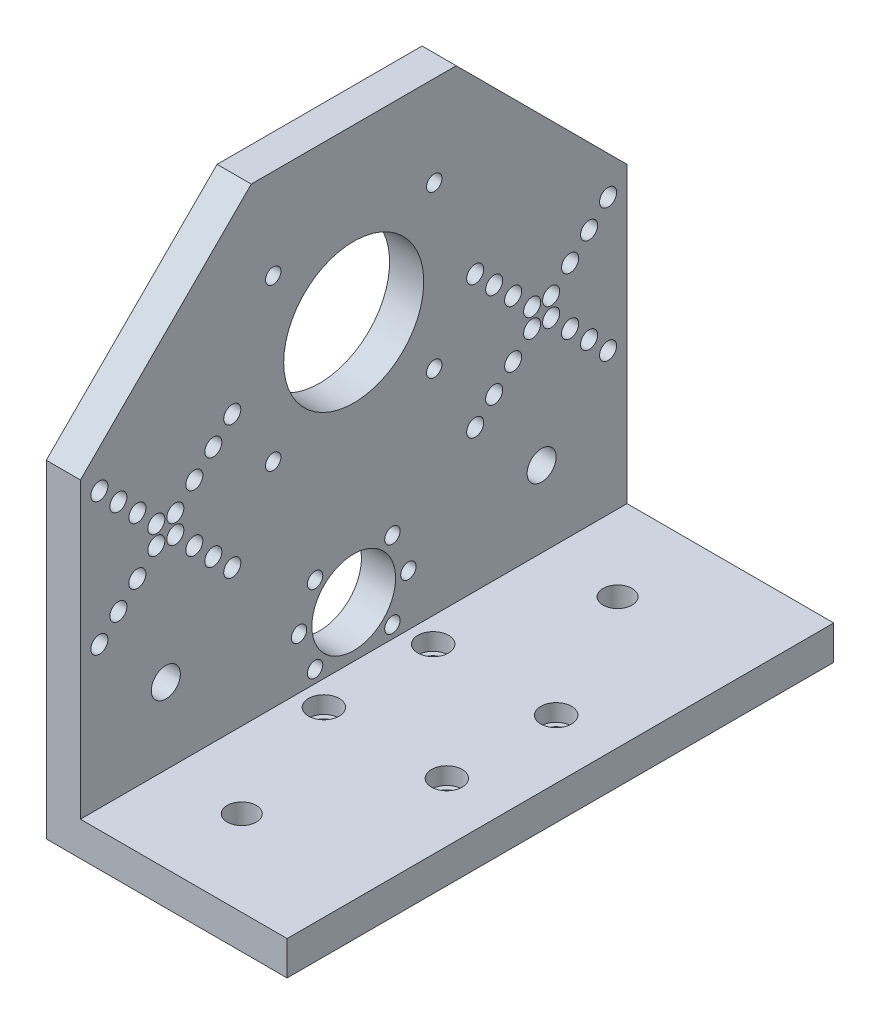
SolidWorks part; units mm, degrees
ref_plane "Front Plane" through (0, 0, 0) normal (0, 0, 1) x (1, 0, 0)
ref_plane "Top Plane" through (0, 0, 0) normal (0, 1, 0) x (1, 0, 0)
ref_plane "Right Plane" through (0, 0, 0) normal (1, 0, 0) x (0, 0, -1)
sketch "Sketch1" plane through (0, 0, 0) normal (0, 1, 0) x (1, 0, 0)
  line L0 (35.25, 46) -> (35.25, 14) construction
  line L1 (0, 0) -> (70.5, 0)
  line L2 (0, 0) -> (0, 60)
  line L3 (0, 60) -> (70.5, 60)
  line L4 (70.5, 0) -> (70.5, 60)
  line L5 (17.25, 46) -> (53.25, 46) construction
  line L6 (17.25, 46) -> (17.25, 14) construction
  line L7 (17.25, 14) -> (53.25, 14) construction
  line L8 (53.25, 46) -> (53.25, 14) construction
  line L9 (17.25, 30) -> (53.25, 30) construction
  circle A2 centre (53.25, 46) radius 2.95
  circle A4 centre (53.25, 14) radius 2.95
  circle A5 centre (17.25, 46) radius 2.95
  circle A6 centre (17.25, 14) radius 2.95
  dimension "D5" = 5.9
  dimension "D1" = 36
  dimension "D2" = 32
  dimension "D3" = 70.5
  dimension "D4" = 60
extrude "Boss-Extrude1" add sketch "Sketch1" along normal blind 10 contours L1 L4 L3 L2 A2 region at (35.25, 0, -30)
sketch "Sketch3" plane through (0, 10, 0) normal (0, 1, 0) x (1, 0, 0)
  circle A1 centre (53.25, 46) radius 4.5
  circle A5 centre (53.25, 14) radius 4.5
  circle A6 centre (17.25, 46) radius 4.5
  circle A7 centre (17.25, 14) radius 4.5
  dimension "D1" = 9
extrude "Cut-Extrude1" cut sketch "Sketch3" against normal blind 5
sketch "Sketch4" plane through (0, 10, 0) normal (0, 1, 0) x (1, 0, 0)
  line L0 (0, 30) -> (10, 30) construction
  line L1 (0, 60) -> (10, 60)
  line L2 (0, 60) -> (0, 0)
  line L3 (0, 0) -> (10, 0)
  line L4 (10, 60) -> (10, 0)
  line L5 (0, 60) -> (70.5, 60) construction
  line L6 (0, 0) -> (70.5, 0) construction
  circle A6 centre (53.25, 14) radius 4.5 construction
  dimension "D1" = 43.25
  dimension "D2" = 10
extrude "Boss-Extrude3" add sketch "Sketch4" along normal blind 31
sketch "Sketch5" plane through (0, 0, 0) normal (-1, 0, 0) x (0, 0, 1)
  line L0 (-30, 41) -> (-30, 10) construction
  line L1 (-60, 41) -> (0, 41) construction
  line L2 (-60, 10) -> (0, 10) construction
  line L3 (-60, 25) -> (0, 25) construction
  line L6 (-60, 41) -> (-60, 0) construction
  line L7 (-30, 25) -> (-18.6863, 36.3137) construction
  line L8 (0, 41) -> (0, 0) construction
  line L9 (0, 10) -> (-60, 10) construction
  line L10 (-30, 25) -> (-18.6863, 13.6863) construction
  circle A0 centre (-30, 25) radius 12.25
  circle A1 centre (-30, 25) radius 16 construction
  circle A2 centre (-14, 25) radius 2.25
  circle A3 centre (-18.6863, 36.3137) radius 2.25
  circle A4 centre (-18.6863, 13.6863) radius 2.25
  circle A5 centre (-41.3137, 36.3137) radius 2.25
  circle A6 centre (-46, 25) radius 2.25
  circle A7 centre (-41.3137, 13.6863) radius 2.25
  dimension "D1" = 24.5
  dimension "D2" = 32
  dimension "D3" = 4.5
  dimension "D5" = 15
  dimension "D6" = 45
  dimension "D7" = 45
  dimension "D4" = 2
extrude "Cut-Extrude2" cut sketch "Sketch5" against normal up to next
sketch "Sketch6" plane through (70.5, 0, 0) normal (1, 0, 0) x (0, 0, -1)
  line L1 (0, 41) -> (60, 41)
  line L2 (0, 41) -> (0, 10)
  line L3 (0, 10) -> (60, 10)
  line L4 (60, 41) -> (60, 10)
  circle A2 centre (30, 25) radius 8
  dimension "D1" = 16
extrude "Boss-Extrude4" add sketch "Sketch6" against normal blind 5
sketch "Sketch7" plane through (0, 41, 0) normal (0, 1, 0) x (1, 0, 0)
  line L1 (0, 60) -> (70.5, 60)
  line L2 (0, 60) -> (0, 0)
  line L3 (0, 0) -> (70.5, 0)
  line L4 (70.5, 60) -> (70.5, 0)
extrude "Boss-Extrude5" add sketch "Sketch7" along normal blind 5
sketch "Sketch8" plane through (0, 0, 0) normal (-1, 0, 0) x (0, 0, 1)
  line L1 (0, 46) -> (0, 0) construction
  line L2 (-60, 46) -> (0, 46)
  line L3 (-60, 46) -> (-60, 146)
  line L4 (-60, 146) -> (0, 146)
  line L5 (0, 46) -> (0, 146)
  line L6 (-53.57, 96) -> (-6.43, 96) construction
  line L7 (-53.57, 119.57) -> (-6.43, 119.57) construction
  line L8 (-53.57, 119.57) -> (-53.57, 72.43) construction
  line L9 (-53.57, 72.43) -> (-6.43, 72.43) construction
  line L10 (-6.43, 119.57) -> (-6.43, 72.43) construction
  line L11 (-30, 119.57) -> (-30, 72.43) construction
  circle A0 centre (-53.57, 72.43) radius 2.25
  circle A1 centre (-6.43, 72.43) radius 2.25
  circle A2 centre (-6.43, 119.57) radius 2.25
  circle A3 centre (-53.57, 119.57) radius 2.25
  circle A4 centre (-30, 96) radius 20.5
  dimension "D4" = 4.5
  dimension "D5" = 41
  dimension "D1" = 100
  dimension "D2" = 47.14
  dimension "D3" = 47.14
extrude "Boss-Extrude6" add sketch "Sketch8" against normal blind 10
sketch "Sketch9" plane through (0, 0, 0) normal (0, 0, 1) x (1, 0, 0)
  line L0 (65.5, 41) -> (65.5, 10) construction
  line L1 (10, 41) -> (65.5, 41) construction
  line L2 (65.5, 41) -> (65.5, 10)
  line L3 (10, 41) -> (65.5, 41)
  line L4 (10, 46) -> (10, 41)
  line L5 (65.5, 10) -> (70.5, 10)
  line L8 (0, 0) -> (70.5, 0)
  line L9 (70.5, 0) -> (70.5, 46)
  line L10 (70.5, 46) -> (10, 46)
  line L11 (10, 46) -> (10, 146)
  line L12 (10, 146) -> (0, 146)
  line L13 (0, 146) -> (0, 0)
  line L16 (0, 0) -> (70.5, 0)
  line L17 (70.5, 0) -> (70.5, 46)
  line L18 (70.5, 46) -> (10, 46)
  line L19 (10, 46) -> (10, 146)
  line L20 (10, 146) -> (0, 146)
  line L21 (0, 146) -> (0, 0)
  line M10 (10, 41) -> (65.5, 41)
  line M11 (65.5, 41) -> (65.5, 10)
  line M14 (70.5, 0) -> (70.5, 46)
  line M15 (70.5, 46) -> (10, 46)
  dimension "D1" = 0
extrude "Cut-Extrude3" cut sketch "Sketch9" against normal up to next contours L5 L4 M11 M14 M15 M10 region at (37.75, 41.704, 0)
sketch "Sketch10" plane through (0, 0, 0) normal (-1, 0, 0) x (0, 0, 1)
  line L0 (-110, 96) -> (-60, 0) construction
  line L1 (-60, 96) -> (-110, 96)
  line L2 (-60, 96) -> (-60, 0)
  line L3 (-60, 0) -> (-110, 0)
  line L4 (-110, 96) -> (-110, 0)
  line L5 (-60, 96) -> (-110, 0) construction
  line L6 (-110, 96) -> (-104.4444, 90.4444) construction
  line L7 (-60, 96) -> (-65.5556, 90.4444) construction
  line L8 (0, 146) -> (-60, 146) construction
  line L9 (-60, 146) -> (-60, 0) construction
  line L10 (0, 0) -> (-60, 0) construction
  circle A0 centre (-110, 96) radius 2.5
  circle A1 centre (-104.4444, 90.4444) radius 2.5
  circle A2 centre (-98.8889, 84.8889) radius 2.5
  circle A3 centre (-93.3333, 79.3333) radius 2.5
  circle A4 centre (-87.7778, 73.7778) radius 2.5
  circle A5 centre (-82.2222, 68.2222) radius 2.5
  circle A6 centre (-76.6667, 62.6667) radius 2.5
  circle A7 centre (-71.1111, 57.1111) radius 2.5
  circle A8 centre (-65.5556, 51.5556) radius 2.5
  circle A9 centre (-60, 46) radius 2.5
  circle A10 centre (-60, 96) radius 2.5
  circle A11 centre (-65.5556, 90.4444) radius 2.5
  circle A12 centre (-71.1111, 84.8889) radius 2.5
  circle A13 centre (-76.6667, 79.3333) radius 2.5
  circle A14 centre (-82.2222, 73.7778) radius 2.5
  circle A15 centre (-87.7778, 68.2222) radius 2.5
  circle A16 centre (-93.3333, 62.6667) radius 2.5
  circle A17 centre (-98.8889, 57.1111) radius 2.5
  circle A18 centre (-104.4444, 51.5556) radius 2.5
  circle A19 centre (-110, 46) radius 2.5
  line M27 (-60, 146) -> (-60, 0)
  dimension "D3" = 5
  dimension "D2" = 50
  dimension "D5" = 50
  dimension "D7" = 50
  dimension "D8" = 50
  dimension "D4" = 10
  dimension "D6" = 10
extrude "Boss-Extrude7" add sketch "Sketch10" against normal up to surface (10 mm away) contours A19 L3 A9 L2 A10 L1 A0 L4 A18 A17 A16 A15 A14 A13 A12 A11 A8 A7 A6 A5 A4 A3 A2 A1 | L1 A10 M27 | L4 A0 L1 | L3 A19 L4 | L2 A9 L3 region at (0, 94.939, -108.939) region at (0, 46.284, -85) region at (0, 94.939, -61.061) region at (0, 46, -108.939) region at (0, 46, -61.061) up to face at (10, 36.3137, -39.0637)
chamfer "Chamfer1" distance 50 angle 45 1 edges at (5, 96, -60)
sketch "Sketch11" plane through (0, 10, 0) normal (0, 1, 0) x (1, 0, 0)
  line L0 (70.5, 60) -> (70.5, 0) construction
  line L1 (10, 60) -> (70.5, 60)
  line L2 (10, 60) -> (10, 110)
  line L3 (10, 110) -> (70.5, 110)
  line L4 (70.5, 60) -> (70.5, 110)
  line L5 (10, 110) -> (0, 110) construction
extrude "Boss-Extrude8" add sketch "Sketch11" against normal blind 10
sketch "Sketch12" plane through (10, 0, 0) normal (1, 0, 0) x (0, 0, -1)
  line L0 (85, 10) -> (85, 48.1) construction
  line L1 (110, 10) -> (0, 10) construction
  line L2 (0, 10) -> (110, 10) construction
  circle A0 centre (85, 32.225) radius 4.25
  circle A1 centre (87.7778, 68.2222) radius 2.5 construction
  point P6 (85, 16.35)
  dimension "D3" = 2.7778
  dimension "D5" = 8.5
  dimension "D1" = 38.1
  dimension "D2" = 6.35
  dimension "D4" = 15.875
extrude "Cut-Extrude4" cut sketch "Sketch12" against normal up to next
sketch "Sketch14" plane through (0, 10, 0) normal (0, 1, 0) x (1, 0, 0)
  line L1 (10, 80.75) -> (10, 89.25) construction
  line L3 (10, 80.75) -> (10, 89.25)
  line L4 (10, 85) -> (32.225, 85) construction
  circle A0 centre (32.225, 85) radius 4.25
  dimension "D2" = 8.5
  dimension "D1" = 22.225
extrude "Cut-Extrude6" cut sketch "Sketch14" against normal up to next contours A0 region at (32.225, 10, -85)
ref_plane "Plane1" through (0, 0, -30) normal (0, 0, 1) x (1, 0, 0)
mirror "Mirror1" about plane through (0, 0, -30) normal (0, 0, 1) of bodies 119
